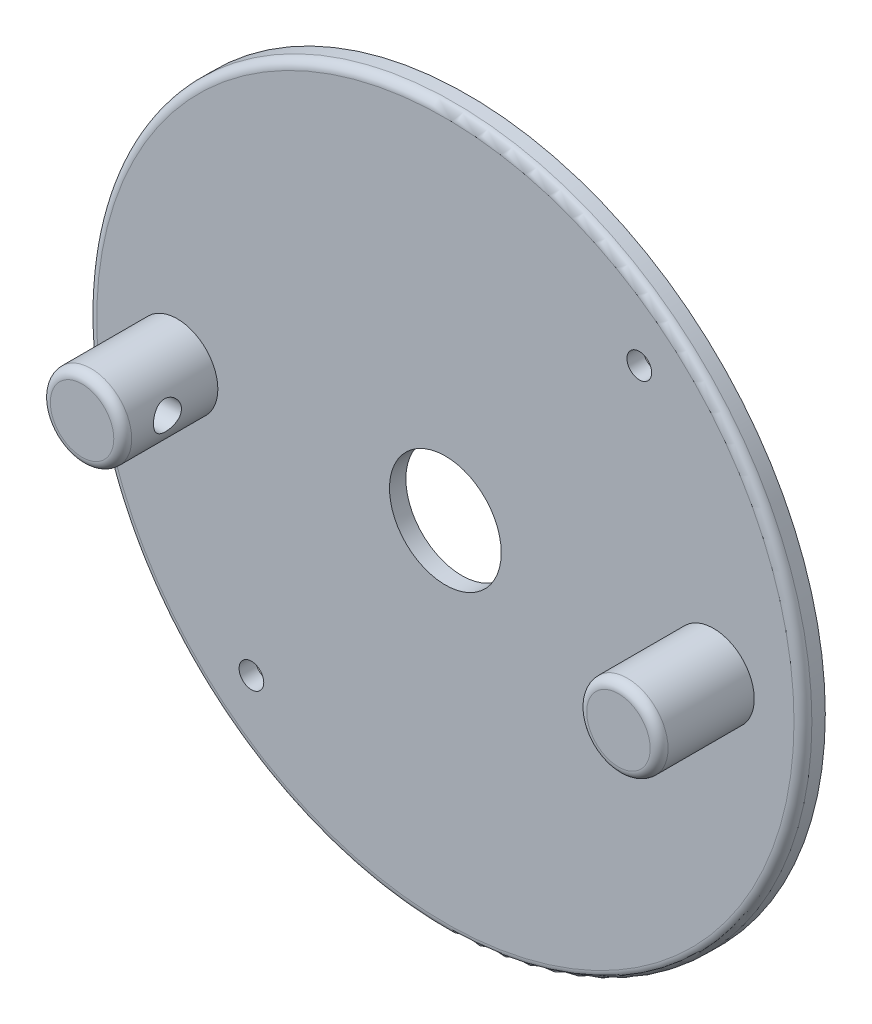
SolidWorks part; units mm, degrees
note: '?' marks a value the reader was unsure of.
material "1060 Alloy"
ref_plane "Front Plane" through (0, 0, 0) normal (0, 0, 1) x (1, 0, 0)
ref_plane "Top Plane" through (0, 0, 0) normal (0, 1, 0) x (1, 0, 0)
ref_plane "Right Plane" through (0, 0, 0) normal (1, 0, 0) x (0, 0, -1)
ref_axis "X-axis" through (-88.99, 0, 0) along (1, 0, 0)?
ref_axis "Y-axis" through (0, 55, 0) along (0, -1, 0)?
ref_axis "Z-axis" through (0, 0, -88.99) along (0, 0, 1)?
sketch "Sketch1" plane through (0, 0, 0) normal (0, 0, 1) x (1, 0, 0)
  circle A0 centre (0, 0) radius 50.8
  dimension "D1" = 101.6
extrude "Boss-Extrude1" add sketch "Sketch1" along normal blind 3.175
sketch "Sketch2" plane through (0, 0, 0) normal (0, 0, -1) x (-1, 0, 0)
  circle A2 centre (0, 0) radius 48.26
  circle A3 centre (0, 0) radius 48.26
  dimension "D1" = 2.54
extrude "Cut-Extrude1" cut sketch "Sketch2" against normal blind 0.8458
sketch "Sketch3" plane through (0, 0, 3.175) normal (0, 0, 1) x (1, 0, 0)
  circle A0 centre (0, 0) radius 7.9375
  dimension "D1" = 15.875
extrude "Cut-Extrude2" cut sketch "Sketch3" against normal blind 21.1328
sketch "Sketch4" plane through (0, 0, 3.175) normal (0, 0, 1) x (1, 0, 0)
  line L0 (0, -54.5116) -> (0, 54.5116) construction
  line L1 (-80.0942, 0) -> (80.0942, 0) construction
  line L2 (-45.1109, -53.7611) -> (45.1109, 53.7611) construction
  circle A0 centre (27.5515, 32.8346) radius 1.7526
  circle A1 centre (-27.5515, -32.8346) radius 1.7526
  point P6 (0, 0)
  point P10 (0, 0)
  point P13 (0, 0)
  dimension "D3" = 3.5052
  dimension "D4" = 3.5052
  dimension "D1" = 50
extrude "Cut-Extrude3" cut sketch "Sketch4" against normal through all
sketch "Sketch5" plane through (0, 0, 3.175) normal (0, 0, 1) x (1, 0, 0)
  line L0 (-86.5709, 0) -> (86.5709, 0) construction
  circle A0 centre (-38.1, 0) radius 5.7785
  circle A1 centre (38.1, 0) radius 5.7785
  point P5 (0, 0)
  dimension "D3" = 11.557
  dimension "D4" = 11.557
  dimension "D1" = 38.1
  dimension "D2" = 38.1
extrude "Boss-Extrude2" add sketch "Sketch5" along normal blind 13.5128
hole_wizard "5/32 (0.15625) Diameter Hole1" positions "3DSketch2" profile "Sketch8" hole size "5/32" standard "ANSI Inch"
sketch3d "3DSketch2"
  point P0 (-32.3252, 0.2055, 10.3296)
  point P2 (-76.1449, -9.8448, 0)
sketch "Sketch8" plane through (-32.3252, 0.2055, 10.3296) normal (0, 0, 1) x (-0.0356, 0.9994, 0)
  line L0 (0, 0) -> (0, 8.7615)
  line L1 (0, 8.7615) -> (1.9844, 7.5692)
  line L2 (1.9844, 7.5692) -> (1.9844, 0)
  line L5 (1.9844, 0) -> (0, 0)
  line L10 (0, 8.7615) -> (-1.9844, 7.5692) construction
  line L11 (0, -6.35) -> (0, 107.95) construction
  dimension "Hole Dia." = 3.9688
  dimension "Hole Depth" = 7.5692
  dimension "Drill Angle" = 118
mirror "Mirror1" about plane through (0, 0, 0) normal (1, 0, 0) of "5/32 (0.15625) Diameter Hole1"
fillet "Fillet1" radius 1.27 2 edges at (43.8785, 0, 16.6878) (-32.3215, 0, 16.6878)
fillet "Fillet2" radius 1.27 1 edges at (50.8, 0, 3.175)
